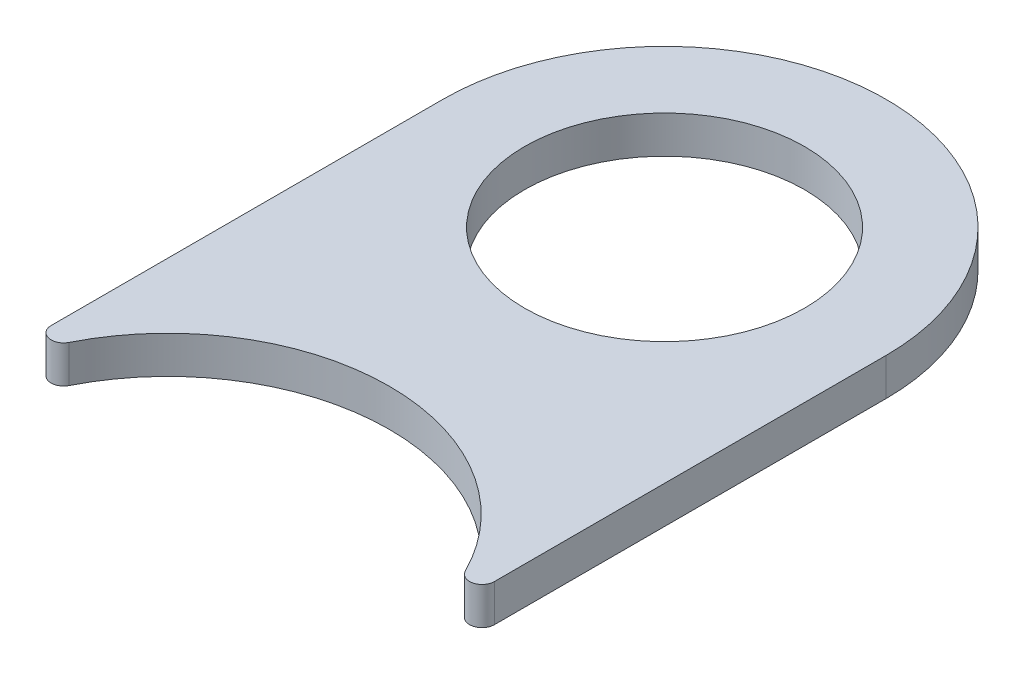
SolidWorks part; units mm, degrees
ref_plane "Front Plane" through (0, 0, 0) normal (0, 0, 1) x (1, 0, 0)
ref_plane "Top Plane" through (0, 0, 0) normal (0, 1, 0) x (1, 0, 0)
ref_plane "Right Plane" through (0, 0, 0) normal (1, 0, 0) x (0, 0, -1)
sketch "Sketch1" plane through (0, 0, 0) normal (0, 1, 0) x (1, 0, 0)
  line L0 (-17.78, 39.8524) -> (-17.78, 0)
  line L1 (17.78, 39.8524) -> (17.78, 0)
  line L2 (-17.78, 0) -> (17.78, 0)
  circle A0 centre (0, 0) radius 17.78
  circle A1 centre (0, 39.8524) radius 17.78
  circle A2 centre (0, 39.8524) radius 11.2304
extrude "Boss-Extrude1" add sketch "Sketch1" along normal blind 3 contours A1 L0 A0 L1 | A1 A2 region at (0, 0, -19.9262) region at (0, 0, -57.1295)
fillet "Fillet1" radius 1 2 edges at (-17.78, 1.5, 0) (17.78, 1.5, 0)
